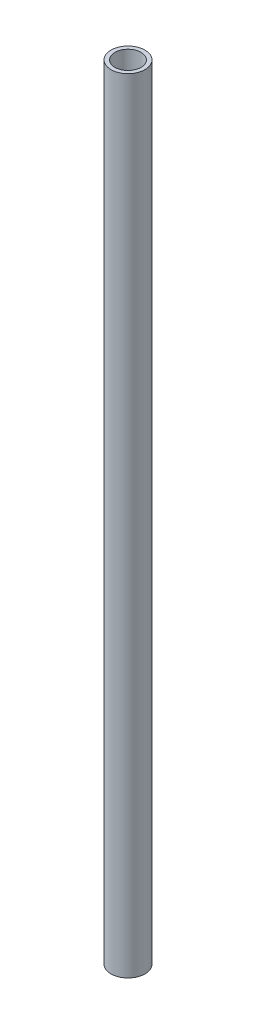
SolidWorks part; units mm, degrees
ref_plane "Płaszczyzna przednia" through (0, 0, 0) normal (0, 0, 1) x (1, 0, 0)
ref_plane "Płaszczyzna górna" through (0, 0, 0) normal (0, 1, 0) x (1, 0, 0)
ref_plane "Płaszczyzna prawa" through (0, 0, 0) normal (1, 0, 0) x (0, 0, -1)
sketch "Sketch1" plane through (0, 0, 0) normal (0, 1, 0) x (1, 0, 0)
  circle A0 centre (0, 0) radius 6.5
  circle A1 centre (0, 0) radius 3.5
  dimension "D1" = 3
  dimension "D2" = 7
extrude "Boss-Extrude1" add sketch "Sketch1" along normal blind 300
sketch "Sketch2" plane through (0, 300, 0) normal (0, 1, 0) x (1, 0, 0)
  circle A1 centre (0, 0) radius 5
  dimension "D1" = 10
extrude "Cut-Extrude1" cut sketch "Sketch2" against normal blind 31
extrude "Cut-Extrude2" cut sketch "Sketch2<2>" along normal blind 31 from surface starting at face at (0, 0, 6.5)
sketch "Sketch2<2>" plane through (0, 300, 0) normal (0, 1, 0) x (1, 0, 0) same geometry as "Sketch2"
equation "\"G\"= 3'grubość ścianki"
equation "\"L\"= 300'długość całkowita"
equation "\"G1\"= 31'głębokość gwintu"
